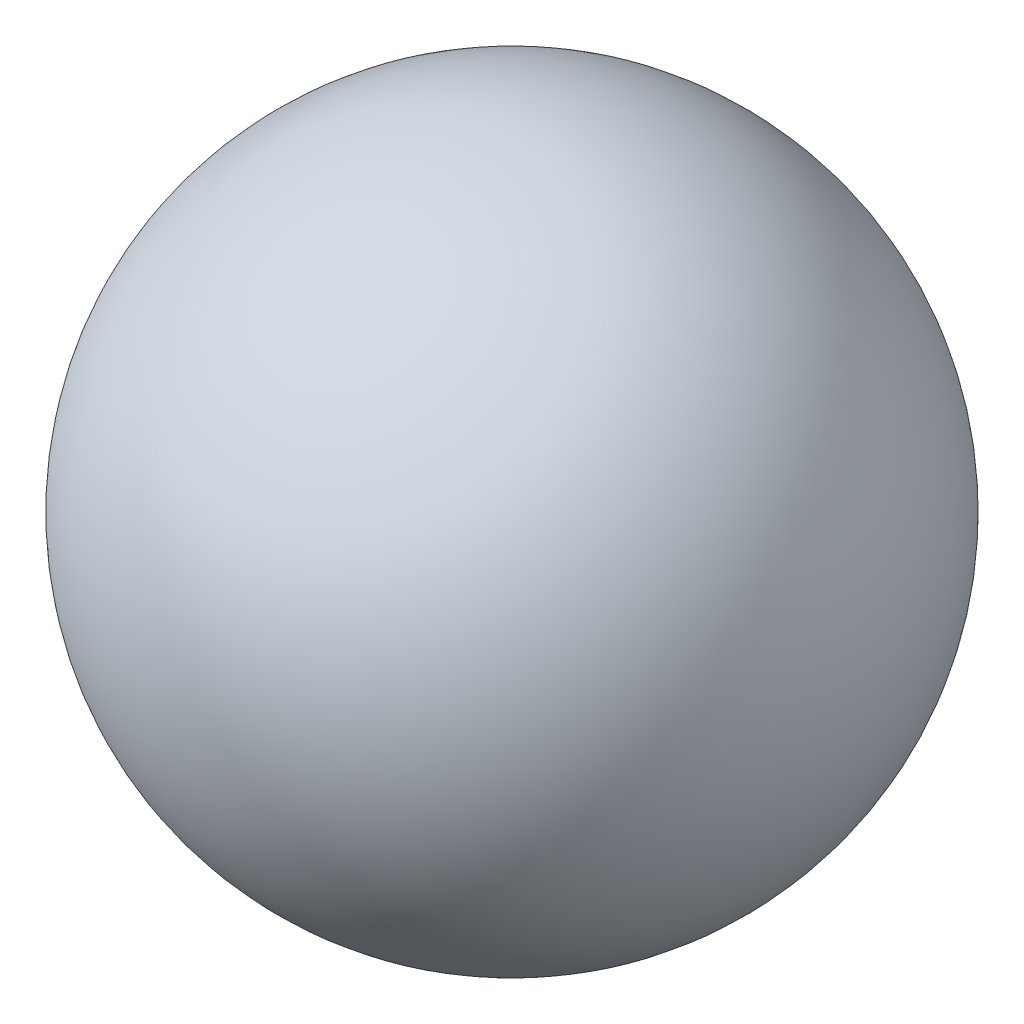
SolidWorks part; units mm, degrees
material "2014 Alloy"
ref_plane "Front Plane" through (0, 0, 0) normal (0, 0, 1) x (1, 0, 0)
ref_plane "Top Plane" through (0, 0, 0) normal (0, 1, 0) x (1, 0, 0)
ref_plane "Right Plane" through (0, 0, 0) normal (1, 0, 0) x (0, 0, -1)
sketch "Sketch1" plane through (0, 0, 0) normal (0, 0, 1) x (1, 0, 0)
  line L0 (0, 0) -> (0, 44.44)
sketch "Sketch2" plane through (0, 0, 0) normal (0, 0, 1) x (1, 0, 0)
  line L0 (0, 10) -> (0, -10)
  arc A0 (0, -10) -> (0, 10) centre (0, 0) ccw
  dimension "D1" = 10
ref_axis "Axis1" through (0, 44.44, 0) along (0, -1, 0)
revolve "Revolve1" add sketch "Sketch2" angle 360 about L0
